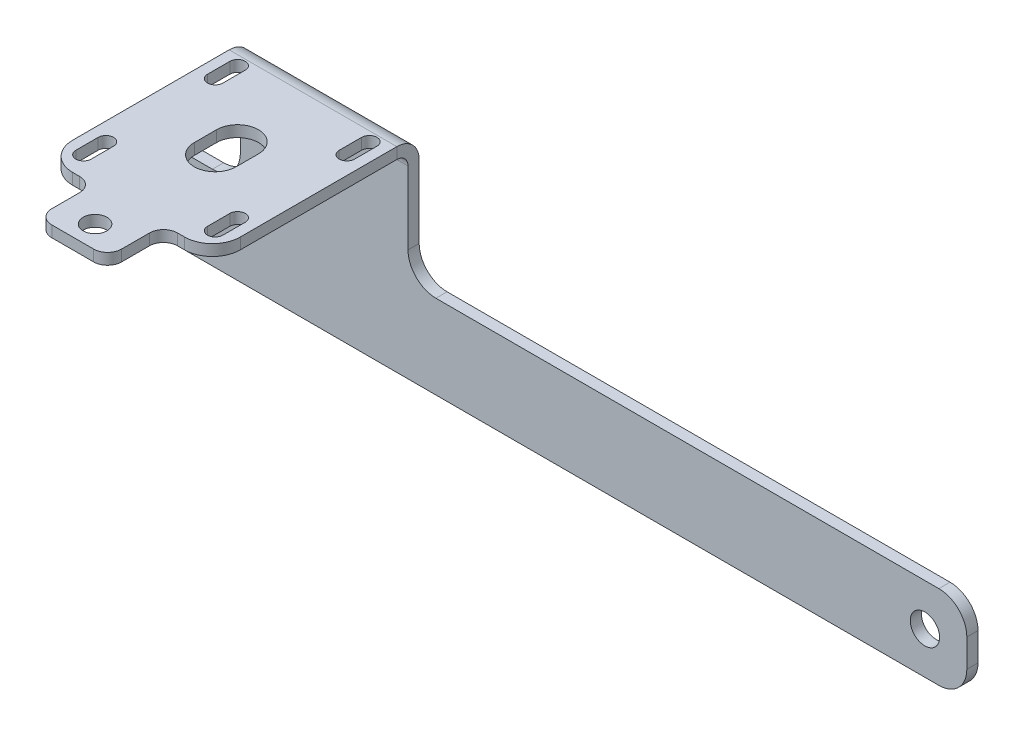
SolidWorks part; units mm, degrees
note: The reader was unsure of these and kept them because the rebuilt part matched: flange length of "Edge-Flange1".
material "ASTM A36 Steel"
ref_plane "Front Plane" through (0, 0, 0) normal (0, 0, 1) x (1, 0, 0)
ref_plane "Top Plane" through (0, 0, 0) normal (0, 1, 0) x (1, 0, 0)
ref_plane "Right Plane" through (0, 0, 0) normal (1, 0, 0) x (0, 0, -1)
sketch "Sketch1" plane through (0, 0, 0) normal (0, 1, 0) x (1, 0, 0)
  line L0 (-23.57, 19.57) -> (-23.57, 27.57) construction
  line L1 (30, -35) -> (17.5, -35)
  line L2 (30, -35) -> (30, 35)
  line L3 (30, 35) -> (-30, 35)
  line L4 (-30, -35) -> (-30, 35)
  line L5 (30, -35) -> (-30, 35) construction
  line L6 (30, 35) -> (-30, -35) construction
  line L7 (-26.32, 19.57) -> (-26.32, 27.57)
  line L8 (-20.82, 19.57) -> (-20.82, 27.57)
  line L9 (26.32, 19.57) -> (26.32, 27.57)
  line L10 (20.82, 19.57) -> (20.82, 27.57)
  line L11 (23.57, 19.57) -> (23.57, 27.57) construction
  line L12 (26.32, -27.57) -> (26.32, -19.57)
  line L13 (20.82, -27.57) -> (20.82, -19.57)
  line L14 (23.57, -27.57) -> (23.57, -19.57) construction
  line L15 (-20.82, -27.57) -> (-20.82, -19.57)
  line L16 (-26.32, -27.57) -> (-26.32, -19.57)
  line L17 (-23.57, -27.57) -> (-23.57, -19.57) construction
  line L18 (0, 4) -> (0, -4) construction
  line L19 (7.5, 4) -> (7.5, -4)
  line L20 (-7.5, 4) -> (-7.5, -4)
  line L21 (-12.5, -40) -> (-12.5, -50)
  line L22 (-7.5, -55) -> (7.5, -55)
  line L23 (12.5, -50) -> (12.5, -40)
  line L24 (-17.5, -35) -> (-30, -35)
  arc A5 (-26.32, 19.57) -> (-20.82, 19.57) centre (-23.57, 19.57) ccw
  arc A6 (-20.82, 27.57) -> (-26.32, 27.57) centre (-23.57, 27.57) ccw
  arc A7 (20.82, 19.57) -> (26.32, 19.57) centre (23.57, 19.57) ccw
  arc A8 (26.32, 27.57) -> (20.82, 27.57) centre (23.57, 27.57) ccw
  arc A9 (20.82, -27.57) -> (26.32, -27.57) centre (23.57, -27.57) ccw
  arc A10 (26.32, -19.57) -> (20.82, -19.57) centre (23.57, -19.57) ccw
  arc A11 (-26.32, -27.57) -> (-20.82, -27.57) centre (-23.57, -27.57) ccw
  arc A12 (-20.82, -19.57) -> (-26.32, -19.57) centre (-23.57, -19.57) ccw
  arc A13 (7.5, 4) -> (-7.5, 4) centre (0, 4) ccw
  arc A14 (-7.5, -4) -> (7.5, -4) centre (0, -4) ccw
  circle A15 centre (0, -47) radius 4.25
  arc A16 (-12.5, -50) -> (-7.5, -55) centre (-7.5, -50) ccw
  arc A17 (7.5, -55) -> (12.5, -50) centre (7.5, -50) ccw
  arc A18 (17.5, -35) -> (12.5, -40) centre (17.5, -40) ccw
  arc A19 (-17.5, -35) -> (-12.5, -40) centre (-17.5, -40) cw
  point P2 (0, 0)
  point P5 (23.57, 23.57)
  point P8 (0, 0)
  point P18 (-23.57, 23.57)
  point P27 (23.57, -23.57)
  point P34 (-23.57, -23.57)
  point P47 (0, -55)
  point P50 (-12.5, -55)
  point P57 (-12.5, -35)
  dimension "D7" = 8.5
  dimension "D9" = 2.75
  dimension "D15" = 12
  dimension "D18" = 5
  dimension "D2" = 23.57
  dimension "D3" = 23.57
  dimension "D4" = 2
  dimension "D5" = 2
  dimension "D6" = 70
  dimension "D8" = 60
  dimension "D10" = 8
  dimension "D11" = 47.14
  dimension "D12" = 47.14
  dimension "D13" = 15
  dimension "D14" = 8
  dimension "D16" = 25
  dimension "D17" = 20
base flange "Base-Flange1" sketch "Sketch1" thickness 4 reverse thickness direction no parameters "D1"=0.7366
edge flange "Edge-Flange1" sketch "Sketch10" flange angle 90 flange length 40 flange position material outside bend radius 4 thickness 4 relief rectangular parameters "D6"=10
sketch "Sketch10" plane through (0, -4, -35) normal (0, 0, -1) x (1, 0, 0)
  line L0 (30, 0) -> (-30, 0) construction
  line L1 (30, 0) -> (-30, 0)
  line L2 (-30, 0) -> (-30, 40)
  line L3 (-30, 40) -> (30, 40)
  line L4 (30, 40) -> (30, 0)
bend "EdgeBend1" bend radius 4 bend angle 90 parameters "D5"=1
sketch "Sketch11" plane through (0, 0, -39) normal (0, 0, -1) x (-1, 0, 0)
  line L0 (-30, -44) -> (-230, -44)
  line L1 (70, -44) -> (30, -44)
  line L2 (70, -44) -> (70, -74)
  line L3 (70, -74) -> (-230, -74)
  line L4 (-230, -44) -> (-230, -74)
  line L8 (30, -8) -> (-30, -8)
  line L9 (-30, -8) -> (-30, -44)
  line L10 (-30, -44) -> (30, -44)
  line L11 (30, -44) -> (30, -8)
  line L12 (30, -8) -> (-30, -8)
  line L13 (-30, -8) -> (-30, -44)
  line L15 (30, -44) -> (30, -8)
  circle A0 centre (-215, -59) radius 5.25
  circle A1 centre (55, -59) radius 5.25
  point P10 (-230, -59)
  dimension "D6" = 10.5
  dimension "D8" = 15
  dimension "D1" = 30
  dimension "D2" = 0
  dimension "D3" = 40
  dimension "D4" = 300
  dimension "D7" = 15
base flange "Tab1" sketch "Sketch11" thickness 4 reverse thickness direction no parameters "D1"=0.7366
fillet "Fillet2" radius 10 8 edges at (-70, -44, -37) (-70, -74, -37) (230, -74, -37) (230, -44, -37) (30, -44, -37) (30, -2, 35) (-30, -2, 35) (-30, -44, -37)
sketch "Bend-Lines1" [suppressed] plane through (0, 0, 0) normal (0, 1, 0) x (1, 0, 0)
sketch "Bounding-Box1" [suppressed] plane through (0, 0, 0) normal (0, 1, 0) x (1, 0, 0)
sheet metal parameters "Sheet-Metal1" thickness 4 parameters "D1"=0.7366
flat pattern "Flat-Pattern1" [suppressed]
sketch "Bend-Lines2" plane through (0, 0, 0) normal (0, 1, 0) x (1, 0, 0)
sketch3d "Bounding-Box2" [suppressed]
  line L0 (31.76, -30, 0) -> (-31.76, -30, 0) construction
  line L1 (31.76, 30, 0) -> (-31.76, 30, 0) construction
  line L2 (31.76, -30, 0) -> (31.76, 30, 0) construction
  line L3 (-31.76, -30, 0) -> (-31.76, 30, 0) construction
sheet metal parameters "Sheet-Metal2" thickness 4 parameters "D1"=0.7366
flat pattern "Flat-Pattern1"
sketch "Bend-Lines2" plane through (0, 0, 0) normal (0, 1, 0) x (1, 0, 0)
  line L0 (31.76, 30.7124) -> (-31.76, 30.7124) construction
  line L1 (31.76, 30.7124) -> (-31.76, 30.7124) construction
sketch3d "Bounding-Box2" [suppressed]
  line L0 (-31.76, 81.4248, 0) -> (-31.76, -30, 0) construction
  line L1 (31.76, 81.4248, 0) -> (31.76, -30, 0) construction
  line L2 (-31.76, 81.4248, 0) -> (31.76, 81.4248, 0) construction
  line L3 (-31.76, -30, 0) -> (31.76, -30, 0) construction
bend of the flat pattern "Flatten-<EdgeBend1>1"
sheet metal parameters "Sheet-Metal3" thickness 4 parameters "D1"=0.7366
flat pattern "Flat-Pattern3"
sketch "Bend-Lines3" plane through (0, 0, 0) normal (0, 1, 0) x (1, 0, 0)
  line L0 (30, 35.7124) -> (-30, 35.7124) construction
  line L1 (30, 35.7124) -> (-30, 35.7124) construction
sketch3d "Bounding-Box3" [suppressed]
  line L0 (212.5, -15, 0) -> (-87.5, -15, 0) construction
  line L1 (212.5, 146.4248, 0) -> (-87.5, 146.4248, 0) construction
  line L2 (212.5, -15, 0) -> (212.5, 146.4248, 0) construction
  line L3 (-87.5, -15, 0) -> (-87.5, 146.4248, 0) construction
bend of the flat pattern "Flatten-<EdgeBend1>2"
